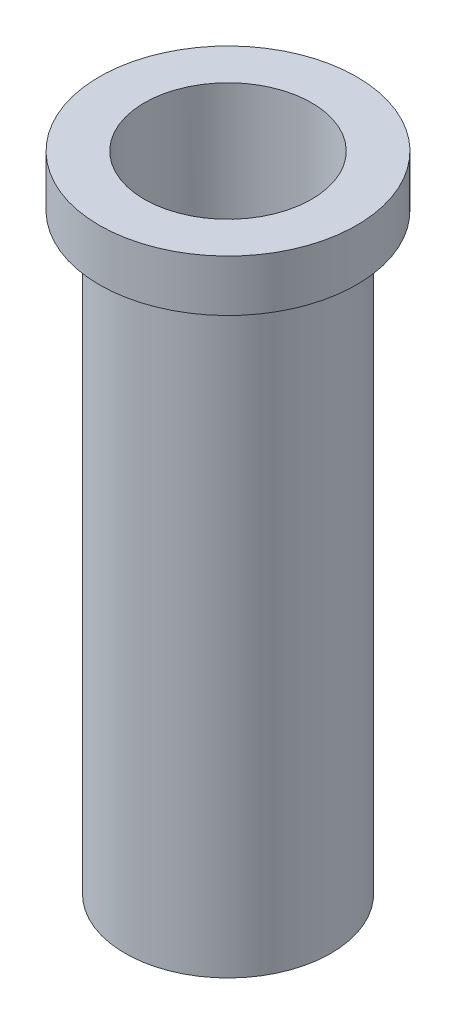
SolidWorks part; units mm, degrees
ref_plane "Ebene vorne" through (0, 0, 0) normal (0, 0, 1) x (1, 0, 0)
ref_plane "Ebene oben" through (0, 0, 0) normal (0, 1, 0) x (1, 0, 0)
ref_plane "Ebene rechts" through (0, 0, 0) normal (1, 0, 0) x (0, 0, -1)
sketch "Skizze1" plane through (0, 0, 0) normal (0, 1, 0) x (1, 0, 0)
  circle A0 centre (0, 0) radius 5
  dimension "D1" = 10
extrude "Aufsatz-Linear austragen1" add sketch "Skizze1" along normal blind 2
sketch "Skizze2" plane through (0, 0, 0) normal (0, -1, 0) x (1, 0, 0)
  circle A0 centre (0, 0) radius 4
  dimension "D1" = 8
extrude "Aufsatz-Linear austragen2" add sketch "Skizze2" along normal blind 23
sketch "Skizze3" plane through (0, 2, 0) normal (0, 1, 0) x (1, 0, 0)
  circle A0 centre (0, 0) radius 3.25
  dimension "D1" = 6.5
extrude "Schnitt-Linear austragen1" cut sketch "Skizze3" against normal offset from surface (23 mm away) 2 up to face at (0, -23, -4)
sketch "Skizze4" plane through (0, -23, 0) normal (0, -1, 0) x (1, 0, 0)
  circle A0 centre (0, 0) radius 1.5
  dimension "D1" = 3
extrude "Schnitt-Linear austragen2" cut sketch "Skizze4" against normal up to surface (2 mm away) up to face at (0, -21, -3.25)
